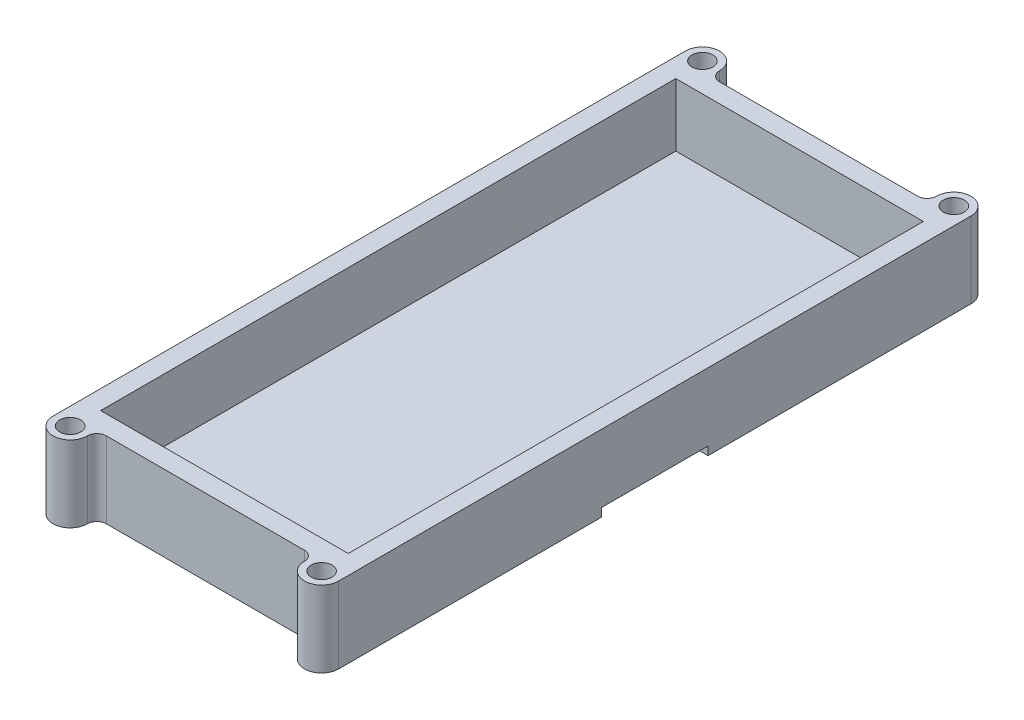
SolidWorks part; units mm, degrees
ref_plane "Front Plane" through (0, 0, 0) normal (0, 0, 1) x (1, 0, 0)
ref_plane "Top Plane" through (0, 0, 0) normal (0, 1, 0) x (1, 0, 0)
ref_plane "Right Plane" through (0, 0, 0) normal (1, 0, 0) x (0, 0, -1)
sketch "Sketch1" plane through (0, 0, 0) normal (0, 1, 0) x (1, 0, 0)
  line L1 (32.5, -75.5) -> (-32.5, -75.5)
  line L2 (32.5, -75.5) -> (32.5, 75.5)
  line L3 (32.5, 75.5) -> (-32.5, 75.5)
  line L4 (-32.5, -75.5) -> (-32.5, 75.5)
  line L9 (-37.5, 75.5) -> (-37.5, -75.5)
  line L10 (0, 7.9485) -> (0, -7.5303) construction
  line L11 (-10.0763, 0) -> (10.4307, 0) construction
  line L13 (37.5, 75.5) -> (37.5, -75.5)
  line L14 (-37.5, -75.5) -> (-37.5, -83)
  line L15 (-28.5, -83) -> (-28.5, -80.5)
  line L16 (-28.5, -80.5) -> (28.5, -80.5)
  line L17 (28.5, -83) -> (28.5, -80.5)
  line L18 (37.5, -75.5) -> (37.5, -83)
  line L19 (28.5, 83) -> (28.5, 80.5)
  line L20 (37.5, 75.5) -> (37.5, 83)
  line L21 (-28.5, 83) -> (-28.5, 80.5)
  line L22 (-37.5, 75.5) -> (-37.5, 83)
  line L23 (-28.5, 80.5) -> (28.5, 80.5)
  arc A0 (-37.5, -83) -> (-28.5, -83) centre (-33, -83) ccw
  circle A1 centre (-33, -83) radius 2.75
  circle A2 centre (33, -83) radius 2.75
  arc A3 (37.5, -83) -> (28.5, -83) centre (33, -83) cw
  circle A4 centre (33, 83) radius 2.75
  arc A5 (37.5, 83) -> (28.5, 83) centre (33, 83) ccw
  circle A6 centre (-33, 83) radius 2.75
  arc A7 (-37.5, 83) -> (-28.5, 83) centre (-33, 83) cw
  point P5 (0, -75.5)
  point P7 (32.5, 0)
  dimension "D5" = 4.5
  dimension "D6" = 5.5
  dimension "D3" = 5
  dimension "D7" = 2.5
  dimension "D1" = 65
  dimension "D2" = 151
  dimension "D4" = 5
extrude "Boss-Extrude1" add sketch "Sketch1" along normal blind 20
sketch "Sketch3" plane through (0, 0, 0) normal (0, -1, 0) x (1, 0, 0)
  line L8 (32.5, -75.5) -> (-32.5, -75.5) construction
  line L9 (-32.5, 75.5) -> (32.5, 75.5)
  line L10 (-32.5, 75.5) -> (-32.5, -75.5)
  line L11 (-32.5, -75.5) -> (32.5, -75.5)
  line L12 (32.5, 75.5) -> (32.5, -75.5)
  line L13 (-32.5, -75.5) -> (-32.5, 75.5) construction
  line L14 (32.5, 75.5) -> (32.5, -75.5) construction
extrude "Boss-Extrude2" add sketch "Sketch3" against normal blind 3.5
sketch "Sketch4" plane through (-37.5, 0, 0) normal (-1, 0, 0) x (0, 0, 1)
  line L0 (-83, 0) -> (83, 0) construction
  line L1 (-13.97, 2.2) -> (13.97, 2.2)
  line L2 (-13.97, 2.2) -> (-13.97, 0)
  line L3 (-13.97, 0) -> (13.97, 0)
  line L4 (13.97, 2.2) -> (13.97, 0)
  point P6 (0, 0)
  point P7 (0, 0)
  dimension "D1" = 27.94
  dimension "D2" = 2.2
extrude "Cut-Extrude1" cut sketch "Sketch4" against normal through all
fillet "Fillet1" radius 2.5 4 edges at (28.5, 10, 80.5) (-28.5, 10, 80.5) (28.5, 10, -80.5) (-28.5, 10, -80.5)
